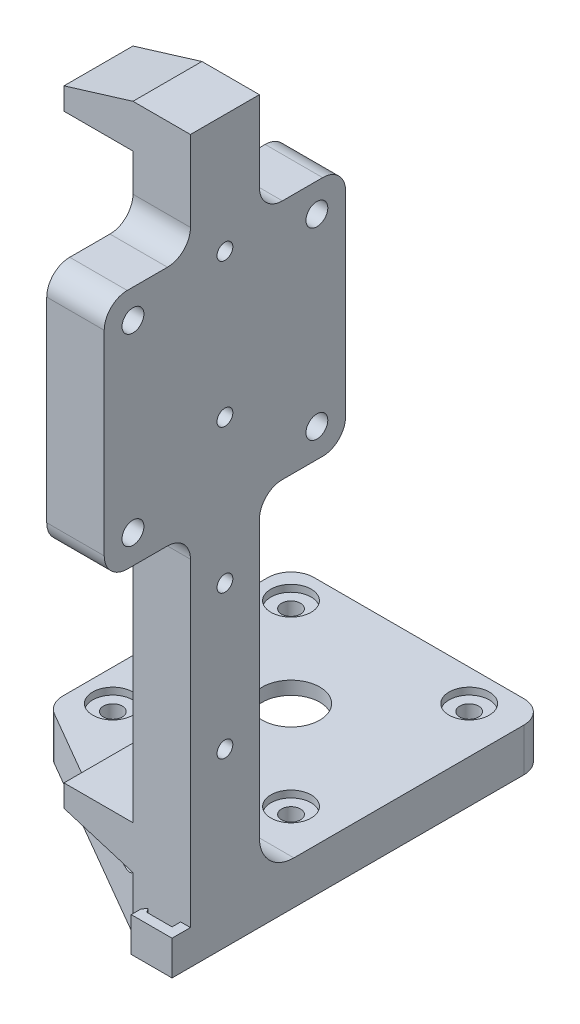
SolidWorks part; units mm, degrees
ref_plane "Front Plane" through (0, 0, 0) normal (0, 0, 1) x (1, 0, 0)
ref_plane "Top Plane" through (0, 0, 0) normal (0, 1, 0) x (1, 0, 0)
ref_plane "Right Plane" through (0, 0, 0) normal (1, 0, 0) x (0, 0, -1)
sketch "Sketch1" plane through (0, 0, 0) normal (1, 0, 0) x (0, 0, -1)
  line L1 (-21, 21) -> (21, 21)
  line L2 (-21, 21) -> (-21, -21)
  line L3 (-21, -21) -> (21, -21)
  line L4 (21, 21) -> (21, -21)
  line L5 (-21, 21) -> (21, -21) construction
  line L6 (-21, -21) -> (21, 21) construction
  circle A0 centre (16, -16) radius 1.9
  circle A1 centre (-16, -16) radius 1.9
  circle A2 centre (-16, 16) radius 1.9
  circle A3 centre (16, 16) radius 1.9
  point P0 (0, 0)
  dimension "D1" = 3.8
  dimension "D2" = 16
  dimension "D5" = 16
  dimension "D6" = 42
  dimension "D3" = 2
  dimension "D4" = 2
extrude "Boss-Extrude1" add sketch "Sketch1" along normal blind 10
sketch "Sketch2" plane through (0, 0, 0) normal (-1, 0, 0) x (0, 0, 1)
  line L0 (21, 21) -> (21, -21) construction
  line L1 (6, 39) -> (-6, 39)
  line L2 (6, 39) -> (6, -79)
  line L3 (6, -79) -> (-6, -79)
  line L4 (-6, 39) -> (-6, -79)
  line L5 (6, 39) -> (-6, -79) construction
  line L6 (6, -79) -> (-6, 39) construction
  line L7 (0, 39) -> (0, -79) construction
  line L8 (-21, 21) -> (21, 21) construction
  point P0 (0, -20)
  dimension "D1" = 12
  dimension "D2" = 21
  dimension "D3" = 118
  dimension "D4" = 18
extrude "Boss-Extrude2" add sketch "Sketch2" against normal blind 10
sketch "Sketch3" plane through (0, 0, 0) normal (-1, 0, 0) x (0, 0, 1)
  line L0 (-6, 31.5) -> (6, 31.5) construction
  line L1 (-6, 39) -> (-6, 21) construction
  line L2 (6, 21) -> (6, 39) construction
  line L3 (6, 39) -> (-6, 39) construction
  line L4 (6, -79) -> (6, -21) construction
  line L5 (6, 31.5) -> (-6, 31.5)
  line L6 (6, 31.5) -> (6, 35.25)
  line L7 (6, 35.25) -> (-6, 35.25)
  line L8 (-6, 31.5) -> (-6, 35.25)
  line L9 (-6, -73.45) -> (6, -73.45)
  line L10 (-6, -73.45) -> (-6, -69.7)
  line L11 (-6, -69.7) -> (6, -69.7)
  line L12 (6, -73.45) -> (6, -69.7)
  dimension "D1" = 7.5
  dimension "D2" = 3.75
  dimension "D3" = 101.2
  dimension "D4" = 3.75
extrude "Boss-Extrude3" add sketch "Sketch3" along normal blind 12
chamfer "Chamfer1" distance 3.75 angle 73 2 edges at (0, 35.25, 0) (0, -73.45, 0) first distance on face at (0, 37.125, 0) first distance on face at (0, -76.225, 0)
sketch "Sketch4" plane through (0, 0, 0) normal (-1, 0, 0) x (0, 0, 1)
  line L0 (0, 31.5) -> (0, -79) construction
  line L1 (-6, 31.5) -> (6, 31.5) construction
  line L2 (-6, -79) -> (6, -79) construction
  circle A0 centre (0, 18.4) radius 1.375
  circle A1 centre (0, -6.6) radius 1.375
  circle A2 centre (0, -31.6) radius 1.375
  circle A3 centre (0, -56.6) radius 1.375
  dimension "D1" = 2.75
  dimension "D2" = 13.1
  dimension "D3" = 4
extrude "Cut-Extrude1" cut sketch "Sketch4" against normal blind 12
sketch "Sketch5" plane through (0, -79, 0) normal (0, -1, 0) x (1, 0, 0)
  line L0 (10, -6) -> (10, 6) construction
  line L1 (10, 6) -> (10, -56)
  line L2 (-34.5, -14) -> (7.5, -14)
  line L3 (-34.5, -14) -> (-34.5, -56)
  line L4 (-34.5, -56) -> (7.5, -56)
  line L5 (7.5, -14) -> (7.5, -56)
  line L6 (-34.5, -14) -> (7.5, -56) construction
  line L7 (-34.5, -56) -> (7.5, -14) construction
  line L8 (10, -56) -> (7.5, -56)
  line L9 (0, 6) -> (-34.5, -14)
  line L10 (0, 6) -> (10, 6)
  circle A0 centre (-13.5, -35) radius 5
  circle A1 centre (2, -50.5) radius 1.65
  circle A2 centre (-29, -50.5) radius 1.65
  circle A3 centre (-29, -19.5) radius 1.65
  circle A4 centre (2, -19.5) radius 1.65
  line M5 (10, 6) -> (0, 6)
  line M7 (0, -6) -> (10, -6)
  line M8 (10, -6) -> (10, 6)
  dimension "D5" = 3.3
  dimension "D9" = 10
  dimension "D1" = 35
  dimension "D2" = 23.5
  dimension "D3" = 42
  dimension "D4" = 42
  dimension "D6" = 15.5
  dimension "D7" = 2
  dimension "D8" = 2
extrude "Boss-Extrude4" add sketch "Sketch5" along normal blind 7.5 contours L5 L2 L3 L4 A4 A3 A2 A1 A0 | L2 L5 L8 L1 M7 | M8 M5 M7 region at (-3.1519, -79, -10.7769) region at (-13.5, -79, -14.594)
sketch "Sketch6" plane through (0, -86.5, 0) normal (0, -1, 0) x (1, 0, 0)
  circle A0 centre (-13.5, -35) radius 12.5
  dimension "D1" = 25
extrude "Cut-Extrude2" cut sketch "Sketch6" against normal blind 5.2
sketch "Sketch7" [suppressed] plane through (10, 0, 0) normal (1, 0, 0) x (0, 0, -1)
  line L0 (-6, 39) -> (6, 39) construction
  line L1 (-1.7321, 15.65) -> (1.7321, 15.65)
  line L2 (1.7321, 15.65) -> (3.4641, 18.65)
  line L3 (3.4641, 18.65) -> (1.7321, 21.65)
  line L4 (1.7321, 21.65) -> (-1.7321, 21.65)
  line L5 (-1.7321, 21.65) -> (-3.4641, 18.65)
  line L6 (-3.4641, 18.65) -> (-1.7321, 15.65)
  line L7 (-1.7321, -9.35) -> (1.7321, -9.35)
  line L8 (1.7321, -9.35) -> (3.4641, -6.35)
  line L9 (3.4641, -6.35) -> (1.7321, -3.35)
  line L10 (1.7321, -3.35) -> (-1.7321, -3.35)
  line L11 (-1.7321, -3.35) -> (-3.4641, -6.35)
  line L12 (-3.4641, -6.35) -> (-1.7321, -9.35)
  line L13 (-1.7321, -34.35) -> (1.7321, -34.35)
  line L14 (1.7321, -34.35) -> (3.4641, -31.35)
  line L15 (3.4641, -31.35) -> (1.7321, -28.35)
  line L16 (1.7321, -28.35) -> (-1.7321, -28.35)
  line L17 (-1.7321, -28.35) -> (-3.4641, -31.35)
  line L18 (-3.4641, -31.35) -> (-1.7321, -34.35)
  line L19 (-1.7321, -59.35) -> (1.7321, -59.35)
  line L20 (1.7321, -59.35) -> (3.4641, -56.35)
  line L21 (3.4641, -56.35) -> (1.7321, -53.35)
  line L22 (1.7321, -53.35) -> (-1.7321, -53.35)
  line L23 (-1.7321, -53.35) -> (-3.4641, -56.35)
  line L24 (-3.4641, -56.35) -> (-1.7321, -59.35)
  circle A0 centre (0, 18.65) radius 3 construction
  dimension "D1" = 6
  dimension "D2" = 4
extrude "Cut-Extrude3" [suppressed] cut sketch "Sketch7" against normal blind 5
fillet "Fillet1" radius 4 11 edges at (10, -82.75, -56) (-34.5, -82.75, -56) (-34.5, -82.75, -14) (5, 21, 6) (5, 21, -6) (5, -21, -6) (5, -21, 6) (5, -21, 21) (5, -21, -21) (5, 21, 21) (5, 21, -21)
fillet "Fillet2" radius 6 2 edges at (5, -79, -6) (0, -79, 0)
sketch "Sketch8" plane through (0, -79, 0) normal (0, 1, 0) x (1, 0, 0)
  circle A0 centre (-29, 50.5) radius 3.5
  circle A2 centre (2, 50.5) radius 3.5
  circle A3 centre (2, 19.5) radius 3.5
  circle A4 centre (-29, 19.5) radius 3.5
  dimension "D1" = 7
  dimension "D2" = 2
  dimension "D3" = 2
extrude "Cut-Extrude4" cut sketch "Sketch8" against normal blind 1.2
sketch "Sketch11" plane through (0, -86.5, 0) normal (0, -1, 0) x (1, 0, 0)
  line L0 (10, 6) -> (10, 9.2)
  line L1 (10, 9.2) -> (2.9, 9.2)
  line L2 (2.9, 9.2) -> (2.9, 7.5)
  line L3 (2.9, 7.5) -> (8.3, 7.5)
  line L4 (8.3, 7.5) -> (8.3, 6)
  line L5 (2.9, 7.5) -> (3.4334, 6.8)
  line L6 (3.4334, 6.8) -> (3.9, 7.5)
  line L7 (3.9, 7.5) -> (2.9, 7.5)
  line L8 (8.3, 6) -> (10, 6)
  line M9 (10, 6) -> (0, 6)
  dimension "D1" = 1.7
  dimension "D2" = 1.7
  dimension "D3" = 5.4
  dimension "D4" = 4.4
  dimension "D5" = 0.7
extrude "Boss-Extrude7" add sketch "Sketch11" against normal blind 6 contours L3 L4 L0 L1 L2 M9 | L5 L6 L3 region at (6.9209, -86.5, 8.0709) region at (3.4111, -86.5, 7.2667)
